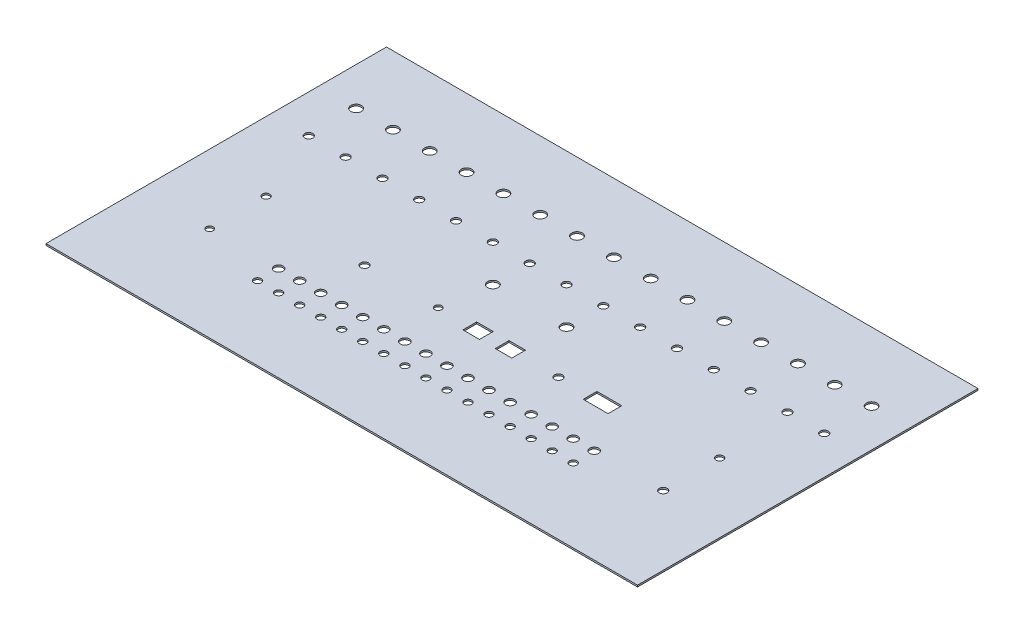
SolidWorks part; units mm, degrees
ref_plane "Front Plane" through (0, 0, 0) normal (0, 0, 1) x (1, 0, 0)
ref_plane "Top Plane" through (0, 0, 0) normal (0, 1, 0) x (1, 0, 0)
ref_plane "Right Plane" through (0, 0, 0) normal (1, 0, 0) x (0, 0, -1)
sketch "Sketch1" plane through (0, 0, 0) normal (0, 1, 0) x (1, 0, 0)
  line L1 (281.15, -161.825) -> (-281.15, -161.825)
  line L2 (281.15, -161.825) -> (281.15, 161.825)
  line L3 (281.15, 161.825) -> (-281.15, 161.825)
  line L4 (-281.15, -161.825) -> (-281.15, 161.825)
  line L5 (281.15, -161.825) -> (-281.15, 161.825) construction
  line L6 (281.15, 161.825) -> (-281.15, -161.825) construction
  point P0 (0, 0)
  dimension "D1" = 323.65
  dimension "D2" = 562.3
extrude "Boss-Extrude1" add sketch "Sketch1" along normal blind 1.5875
sketch "Sketch6" plane through (0, 1.5875, 0) normal (0, 1, 0) x (1, 0, 0)
  line L0 (-281.15, 161.825) -> (-281.15, -161.825) construction
  line L1 (-281.15, -161.825) -> (281.15, -161.825) construction
  circle A0 centre (-150, -91.825) radius 3.5
  dimension "D1" = 131.15
  dimension "D2" = 70
extrude "Cut-Extrude2" cut sketch "Sketch6" against normal up to next
pattern_linear "LPattern2" count 16 spacing 20 along (1, 0, 0) of "Cut-Extrude2"
sketch "Sketch7" plane through (0, 1.5875, 0) normal (0, 1, 0) x (1, 0, 0)
  line L0 (-281.15, 161.825) -> (-281.15, -161.825) construction
  circle A0 centre (-150, -71.825) radius 4.25
  circle A1 centre (-150, -91.825) radius 3.5 construction
  dimension "D1" = 131.15
  dimension "D3" = 8.5
  dimension "D2" = 20
extrude "Cut-Extrude3" cut sketch "Sketch7" against normal up to next
pattern_linear "LPattern3" count 16 spacing 20 along (1, 0, 0) of "Cut-Extrude3"
sketch "Sketch8" plane through (0, 1.5875, 0) normal (0, 1, 0) x (1, 0, 0)
  line L1 (-281.15, 161.825) -> (-281.15, -161.825) construction
  line L2 (-281.15, -161.825) -> (281.15, -161.825) construction
  circle A0 centre (-215.575, -71.825) radius 3.3
  dimension "D1" = 90
  dimension "D2" = 65.575
extrude "Cut-Extrude4" cut sketch "Sketch8" against normal up to next
sketch "Sketch12" plane through (0, 1.5875, 0) normal (0, 1, 0) x (1, 0, 0)
  text T0 "BPM Control\r\n\r\n"
sketch "Sketch13" plane through (0, 1.5875, 0) normal (0, 1, 0) x (1, 0, 0)
  text T0 "Channel Select"
sketch "Sketch14" plane through (0, 1.5875, 0) normal (0, 1, 0) x (1, 0, 0)
  text T0 "Master Volume\r\n"
sketch "Sketch15" plane through (0, 1.5875, 0) normal (0, 1, 0) x (1, 0, 0)
  line L0 (281.15, 161.825) -> (-281.15, 161.825) construction
  line L1 (126.0074, -34.715) -> (102.3974, -34.715)
  line L2 (126.0074, -34.715) -> (126.0074, -21.635)
  line L3 (126.0074, -21.635) -> (102.3974, -21.635)
  line L4 (102.3974, -34.715) -> (102.3974, -21.635)
  line L5 (126.0074, -34.715) -> (102.3974, -21.635) construction
  line L6 (126.0074, -21.635) -> (102.3974, -34.715) construction
  point P0 (114.2024, -28.175)
  dimension "D1" = 13.08
  dimension "D2" = 23.61
  dimension "D3" = 190
extrude "Cut-Extrude7" cut sketch "Sketch15" against normal up to next
sketch "Sketch16" plane through (0, 1.5875, 0) normal (0, 1, 0) x (1, 0, 0)
  line L0 (281.15, 161.825) -> (-281.15, 161.825) construction
  circle A0 centre (-41.9525, -28.175) radius 3.3
  dimension "D1" = 190
extrude "Cut-Extrude8" cut sketch "Sketch16" against normal up to next contours A0
sketch "Sketch17" plane through (0, 1.5875, 0) normal (0, 1, 0) x (1, 0, 0)
  text T0 "Loop Back Control\r\n"
sketch "Sketch18" plane through (0, 1.5875, 0) normal (0, 1, 0) x (1, 0, 0)
  line L0 (102.3974, -34.715) -> (126.0074, -34.715) construction
  line L1 (3.7875, -34.715) -> (-11.9525, -34.715)
  line L2 (3.7875, -34.715) -> (3.7875, -21.635)
  line L3 (3.7875, -21.635) -> (-11.9525, -21.635)
  line L4 (-11.9525, -34.715) -> (-11.9525, -21.635)
  line L5 (3.7875, -34.715) -> (-11.9525, -21.635) construction
  line L6 (3.7875, -21.635) -> (-11.9525, -34.715) construction
  point P0 (-4.0825, -28.175)
  dimension "D1" = 13.08
  dimension "D2" = 15.74
  dimension "D3" = 0
extrude "Cut-Extrude9" cut sketch "Sketch18" against normal up to next
sketch "Sketch19" plane through (0, 1.5875, 0) normal (0, 1, 0) x (1, 0, 0)
  line L1 (34.5275, -34.715) -> (18.7875, -34.715)
  line L2 (34.5275, -34.715) -> (34.5275, -21.635)
  line L3 (34.5275, -21.635) -> (18.7875, -21.635)
  line L4 (18.7875, -34.715) -> (18.7875, -21.635)
  line L5 (34.5275, -34.715) -> (18.7875, -21.635) construction
  line L6 (34.5275, -21.635) -> (18.7875, -34.715) construction
  line L7 (-11.9525, -34.715) -> (3.7875, -34.715) construction
  line L8 (3.7875, -34.715) -> (3.7875, -21.635) construction
  point P0 (26.6575, -28.175)
  dimension "D4" = 15
  dimension "D1" = 13.08
  dimension "D2" = 15.74
  dimension "D3" = 0
extrude "Cut-Extrude10" cut sketch "Sketch19" against normal up to next
sketch "Sketch20" plane through (0, 1.5875, 0) normal (0, 1, 0) x (1, 0, 0)
  text T0 "Loop Back"
sketch "Sketch21" plane through (0, 1.5875, 0) normal (0, 1, 0) x (1, 0, 0)
  text T0 "Current Position"
sketch "Sketch23" plane through (0, 1.5875, 0) normal (0, 1, 0) x (1, 0, 0)
  text T0 "Measure Select"
sketch "Sketch24" plane through (0, 1.5875, 0) normal (0, 1, 0) x (1, 0, 0)
  line L0 (-281.15, 161.825) -> (-281.15, -161.825) construction
  line L1 (281.15, 161.825) -> (-281.15, 161.825) construction
  circle A0 centre (-215.57, -18.175) radius 3.5
  text T0 "Start/Stop"
  dimension "D1" = 65.58
  dimension "D2" = 180
extrude "Cut-Extrude12" cut sketch "Sketch24" against normal up to next contours A0
sketch "Sketch25" plane through (0, 1.5875, 0) normal (0, 1, 0) x (1, 0, 0)
  text T0 "Start/Stop\r\n"
sketch "Sketch26" plane through (0, 1.5875, 0) normal (0, 1, 0) x (1, 0, 0)
  line L0 (281.15, -161.825) -> (281.15, 161.825) construction
  line L1 (281.15, 161.825) -> (-281.15, 161.825) construction
  circle A0 centre (215.57, -18.175) radius 3.5
  dimension "D1" = 65.58
  dimension "D2" = 180
extrude "Cut-Extrude13" cut sketch "Sketch26" against normal up to next
sketch "Sketch27" plane through (0, 1.5875, 0) normal (0, 1, 0) x (1, 0, 0)
  text T0 "Reset"
hole_wizard "M7 Clearance Hole1" positions "Sketch30" profile "Sketch31" hole size "M7" standard "ANSI Metric" end condition through all
sketch "Sketch30" plane through (0, 1.5875, 0) normal (0, 1, 0) x (1, 0, 0)
  line L0 (-281.15, 161.825) -> (-281.15, -161.825) construction
  line L1 (281.15, 161.825) -> (-281.15, 161.825) construction
  point P0 (-245, 51.825)
  dimension "D1" = 36.15
  dimension "D2" = 110
sketch "Sketch31" plane through (-245, 1.5875, -51.825) normal (1, 0, 0) x (0, 0, 1)
  line L0 (0, 0) -> (0, 1.5875)
  line L1 (0, 1.5875) -> (3.8, 1.5875)
  line L2 (3.8, 1.5875) -> (3.8, 0)
  line L5 (3.8, 0) -> (0, 0)
  line L11 (0, -6.35) -> (0, 107.95) construction
  dimension "Thru Hole Dia." = 7.6
  dimension "Thru Hole Depth" = 1.5875
pattern_linear "LPattern4" count 15 spacing 35 along (1, 0, 0) of "M7 Clearance Hole1"
sketch "Sketch33" plane through (0, 1.5875, 0) normal (0, 1, 0) x (1, 0, 0)
  circle A0 centre (-245, 96.825) radius 5
  circle A1 centre (-245, 51.825) radius 3.8 construction
  dimension "D1" = 45
  dimension "D2" = 0
extrude "Cut-Extrude14" cut sketch "Sketch33" against normal up to next
pattern_linear "LPattern5" count 15 spacing 35 along (1, 0, 0) of "Cut-Extrude14"
sketch "Sketch34" plane through (0, 1.5875, 0) normal (0, 1, 0) x (1, 0, 0)
  circle A0 centre (-35, 16.825) radius 5
  circle A1 centre (-35, 51.825) radius 3.8 construction
  circle A2 centre (-70, 51.825) radius 3.8 construction
  dimension "D1" = 35
  dimension "D2" = 35
extrude "Cut-Extrude15" cut sketch "Sketch34" against normal up to next
pattern_linear "LPattern6" count 2 spacing 70 along (1, 0, 0) of "Cut-Extrude15"
hole_wizard "M7 Clearance Hole3" positions "Sketch37" profile "Sketch38" hole size "M7" standard "ANSI Metric" end condition through all
sketch "Sketch37" plane through (0, 1.5875, 0) normal (0, 1, 0) x (1, 0, 0)
  line L0 (102.3974, -21.635) -> (102.3974, -34.715) construction
  line L2 (126.0074, -21.635) -> (102.3974, -21.635) construction
  point P0 (72.3974, -28.165)
  point P5 (102.3974, -28.175)
  dimension "D1" = 30
  dimension "D2" = 6.53
sketch "Sketch38" plane through (72.3974, 1.5875, 28.165) normal (1, 0, 0) x (0, 0, 1)
  line L0 (0, 0) -> (0, 1.5875)
  line L1 (0, 1.5875) -> (3.8, 1.5875)
  line L2 (3.8, 1.5875) -> (3.8, 0)
  line L5 (3.8, 0) -> (0, 0)
  line L11 (0, -6.35) -> (0, 107.95) construction
  dimension "Thru Hole Dia." = 7.6
  dimension "Thru Hole Depth" = 1.5875
hole_wizard "M7 Clearance Hole4" positions "Sketch39" profile "Sketch40" hole size "M7" standard "ANSI Metric" end condition through all
sketch "Sketch39" plane through (0, 1.5875, 0) normal (0, 1, 0) x (1, 0, 0)
  line L0 (281.15, 161.825) -> (-281.15, 161.825) construction
  circle A0 centre (-41.9525, -28.175) radius 3.3 construction
  point P0 (-111.9525, -28.175)
  dimension "D1" = 70
  dimension "D2" = 190
sketch "Sketch40" plane through (-111.9525, 1.5875, 28.175) normal (1, 0, 0) x (0, 0, 1)
  line L0 (0, 0) -> (0, 1.5875)
  line L1 (0, 1.5875) -> (3.8, 1.5875)
  line L2 (3.8, 1.5875) -> (3.8, 0)
  line L5 (3.8, 0) -> (0, 0)
  line L11 (0, -6.35) -> (0, 107.95) construction
  dimension "Thru Hole Dia." = 7.6
  dimension "Thru Hole Depth" = 1.5875
hole_wizard "M7 Clearance Hole5" positions "Sketch41" profile "Sketch42" hole size "M7" standard "ANSI Metric" end condition through all
sketch "Sketch41" plane through (0, 1.5875, 0) normal (0, 1, 0) x (1, 0, 0)
  line L0 (-281.15, -161.825) -> (281.15, -161.825) construction
  line L1 (281.15, -161.825) -> (281.15, 161.825) construction
  point P0 (215.57, -71.825)
  dimension "D1" = 90
  dimension "D2" = 65.58
sketch "Sketch42" plane through (215.57, 1.5875, 71.825) normal (1, 0, 0) x (0, 0, 1)
  line L0 (0, 0) -> (0, 1.5875)
  line L1 (0, 1.5875) -> (3.8, 1.5875)
  line L2 (3.8, 1.5875) -> (3.8, 0)
  line L5 (3.8, 0) -> (0, 0)
  line L11 (0, -6.35) -> (0, 107.95) construction
  dimension "Thru Hole Dia." = 7.6
  dimension "Thru Hole Depth" = 1.5875
